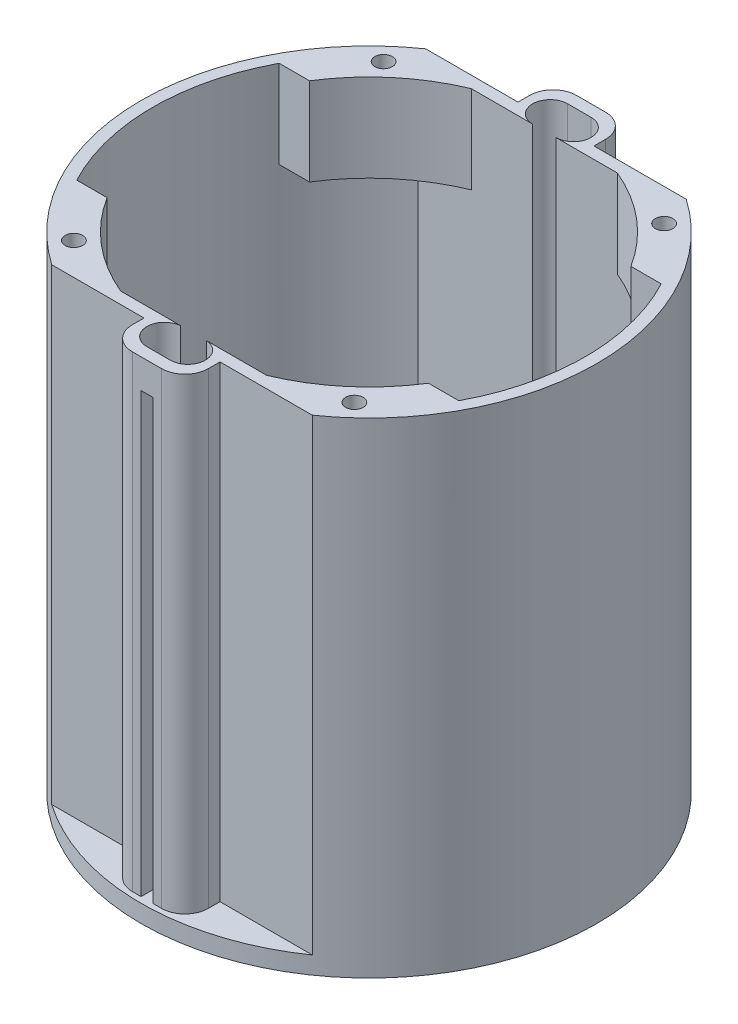
SolidWorks part; units mm, degrees
note: The reader was unsure of these and kept them because the rebuilt part matched: shared geometry of "Croquis1<4>".
material "ABS"
ref_plane "Alzado" through (0, 0, 0) normal (0, 0, 1) x (1, 0, 0)
ref_plane "Planta" through (0, 0, 0) normal (0, 1, 0) x (1, 0, 0)
ref_plane "Vista lateral" through (0, 0, 0) normal (1, 0, 0) x (0, 0, -1)
sketch "Croquis1" plane through (0, 0, 0) normal (0, 1, 0) x (1, 0, 0)
  line L0 (0, 0) -> (73.258, 0) construction
  line L1 (0, 0) -> (0, -19.9451) construction
  line L2 (27.5, 27.6541) -> (27.5, 17.3205)
  line L3 (24.9199, 30) -> (12.5, 30)
  line L4 (-27.5, -27.6541) -> (-27.5, -17.3205)
  line L5 (-27.5, 27.6541) -> (-27.5, 17.3205)
  line L6 (-24.9199, 30) -> (-12.5, 30)
  line L7 (-24.9199, -30) -> (-12.5, -30)
  line L8 (24.9199, -30) -> (12.5, -30)
  line L9 (27.5, -27.6541) -> (27.5, -17.3205)
  arc A0 (-24.9199, 30) -> (-27.5, 27.6541) centre (0, 0) ccw
  circle A1 centre (0, 0) radius 47
  circle A2 centre (0, 0) radius 30
  arc A3 (-12.5, 30) -> (-27.5, 17.3205) centre (0, 0) ccw
  arc A4 (12.5, 30) -> (27.5, 17.3205) centre (0, 0) cw
  arc A6 (24.9199, 30) -> (27.5, 27.6541) centre (0, 0) cw
  arc A7 (-12.5, -30) -> (-27.5, -17.3205) centre (0, 0) cw
  arc A8 (-24.9199, -30) -> (-27.5, -27.6541) centre (0, 0) cw
  arc A9 (-27.5, -27.6541) -> (-24.9199, -30) centre (0, 0) ccw
  arc A10 (24.9199, -30) -> (27.5, -27.6541) centre (0, 0) ccw
  arc A11 (27.5, 27.6541) -> (24.9199, 30) centre (0, 0) ccw
  arc A12 (12.5, -30) -> (27.5, -17.3205) centre (0, 0) ccw
  dimension "D3" = 60
  dimension "D4" = 78
extrude "Saliente-Extruir2" add sketch "Croquis1" along normal blind 80 contours A3 L6 A0 L5 | A8 L7 A7 L4 | A12 L8 A10 L9 | A6 L3 A4 L2
extrude "Saliente-Extruir3" add sketch "Croquis1<4>" against normal blind 3 separate body contours A1 A2 L6 A3 L5 A0 L3 A6 L2 A4 L7 A8 L4 A7 L8 A12 L9 A10 | A2
sketch "Croquis1<4>" plane through (0, 0, 0) normal (0, 1, 0) x (1, 0, 0) same geometry as "Croquis1"
sketch "Croquis2" plane through (0, -3, 0) normal (0, -1, 0) x (1, 0, 0)
  circle A0 centre (0, 0) radius 47
extrude "Saliente-Extruir4" add sketch "Croquis2" against normal up to surface (3 mm away) up to face at (0, 0, 47)
sketch "Croquis3" plane through (0, 80, 0) normal (0, 1, 0) x (1, 0, 0)
  line L0 (-24.9199, 30) -> (-12.5, 30) construction
  line L3 (-27.5, 27.6541) -> (-27.5, 17.3205) construction
  line L4 (0, 0) -> (0, 48.5429) construction
  line L5 (0, 0) -> (-54.4574, 0) construction
  circle A0 centre (-24, 26.5) radius 1.5
  circle A1 centre (24, 26.5) radius 1.5
  circle A2 centre (-24, -26.5) radius 1.5
  circle A3 centre (24, -26.5) radius 1.5
  dimension "D1" = 3.5
  dimension "D3" = 3
  dimension "D2" = 3.5
extrude "Cortar-Extruir1" cut sketch "Croquis3" against normal blind 7
sketch "Croquis4" plane through (0, 0, 0) normal (0, 1, 0) x (1, 0, 0)
  line L0 (-6.5, 30) -> (-4, 30)
  line L1 (-12.5, -30) -> (12.5, -30)
  line L2 (0, 0) -> (57.4423, 0) construction
  line L3 (1, 36) -> (2, 36)
  line L9 (4, 30) -> (6.5, 30)
  line L14 (-1, 38) -> (-2.5, 38)
  line L15 (-6.5, 34) -> (-6.5, 30)
  line L16 (-6.5, 30) -> (-2, 30)
  line L17 (6.5, 30) -> (6.5, 34)
  line L18 (2.5, 38) -> (1, 38)
  line L19 (-2, 36) -> (-1, 36)
  line L20 (-1, 38) -> (-1, 36)
  line L21 (1, 38) -> (1, 36)
  line L22 (0, 37.1225) -> (0, 41.9613) construction
  line L23 (2, 30) -> (6.5, 30)
  line L25 (-12.5, 30) -> (12.5, 30)
  line L34 (2, -30) -> (6.5, -30)
  line L36 (1, -38) -> (1, -36)
  line L37 (-1, -38) -> (-1, -36)
  line L38 (-2, -36) -> (-1, -36)
  line L39 (2.5, -38) -> (1, -38)
  line L40 (6.5, -30) -> (6.5, -34)
  line L41 (-6.5, -30) -> (-2, -30)
  line L42 (-6.5, -34) -> (-6.5, -30)
  line L43 (-1, -38) -> (-2.5, -38)
  line L44 (4, -30) -> (6.5, -30)
  line L45 (1, -36) -> (2, -36)
  line L46 (-6.5, -30) -> (-4, -30)
  line L47 (-6.5, -30) -> (-2, -30)
  circle A0 centre (0, 0) radius 39
  arc A3 (2, 30) -> (2, 36) centre (2, 33) ccw
  arc A4 (-2, 36) -> (-2, 30) centre (-2, 33) ccw
  arc A6 (-2.5, 38) -> (-6.5, 34) centre (-2.5, 34) ccw
  arc A7 (2.232, 30.009) -> (2.5, 30) centre (2.5, 34) ccw
  arc A8 (-2.5, 30) -> (-2.232, 30.009) centre (-2.5, 34) ccw
  arc A9 (6.5, 34) -> (2.5, 38) centre (2.5, 34) ccw
  arc A14 (6.5, -34) -> (2.5, -38) centre (2.5, -34) cw
  arc A15 (-2.5, -30) -> (-2.232, -30.009) centre (-2.5, -34) cw
  arc A16 (2.232, -30.009) -> (2.5, -30) centre (2.5, -34) cw
  arc A17 (-2.5, -38) -> (-6.5, -34) centre (-2.5, -34) cw
  arc A18 (-2, -36) -> (-2, -30) centre (-2, -33) cw
  arc A19 (2, -30) -> (2, -36) centre (2, -33) cw
  dimension "D1" = 4
  dimension "D4" = 4
  dimension "D3" = 4.5
  dimension "D5" = 4
  dimension "D2" = 4.5
extrude "Saliente-Extruir6" add sketch "Croquis4" along normal blind 80 contours A16 A19 L45 L36 L39 A14 L40 L34 | L38 A18 A15 L41 L1 L42 A17 L43 L37 | L23 A3 L3 L21 L18 A9 L17 | L16 A4 L19 L20 L14 A6 L15
sketch "Croquis8" plane through (0, 0, 30) normal (0, 0, 1) x (1, 0, 0)
  line L0 (-24.9199, 80) -> (-6.5, 80)
  line L1 (-6.5, 80) -> (-6.5, 77)
  line L2 (-6.5, 77) -> (-24.9199, 77)
  line L3 (-24.9199, 80) -> (-24.9199, 0) construction
  line L4 (-24.9199, 77) -> (-24.9199, 80)
extrude "Saliente-Extruir7" add sketch "Croquis8" along normal blind 2
sketch "Croquis9" plane through (0, 0, 30) normal (0, 0, 1) x (1, 0, 0)
  line L0 (24.9199, 80) -> (6.5, 80)
  line L1 (6.5, 80) -> (6.5, 77)
  line L2 (6.5, 80) -> (6.5, 0) construction
  line L3 (6.5, 77) -> (24.9199, 77)
  line L4 (24.9199, 80) -> (24.9199, 0) construction
  line L5 (24.9199, 77) -> (24.9199, 80)
extrude "Saliente-Extruir8" add sketch "Croquis9" along normal blind 2
sketch "Croquis10" plane through (0, 0, -30) normal (0, 0, -1) x (-1, 0, 0)
  line L0 (24.9199, 80) -> (6.5, 80)
  line L1 (6.5, 80) -> (6.5, 77)
  line L2 (6.5, 77) -> (24.9199, 77)
  line L3 (24.9199, 80) -> (24.9199, 0) construction
  line L4 (24.9199, 77) -> (24.9199, 80)
extrude "Saliente-Extruir9" add sketch "Croquis10" along normal blind 2
sketch "Croquis11" plane through (0, 0, -30) normal (0, 0, -1) x (-1, 0, 0)
  line L0 (-24.9199, 80) -> (-6.5, 80)
  line L1 (-6.5, 80) -> (-6.5, 77)
  line L2 (-6.5, 80) -> (-6.5, 0) construction
  line L3 (-6.5, 77) -> (-24.9199, 77)
  line L4 (-24.9199, 80) -> (-24.9199, 0) construction
  line L5 (-24.9199, 77) -> (-24.9199, 80)
extrude "Saliente-Extruir10" add sketch "Croquis11" along normal blind 2
sketch "Croquis12" plane through (0, 80, 0) normal (0, 1, 0) x (1, 0, 0)
  circle A0 centre (0, 0) radius 39
  circle A1 centre (0, 0) radius 40.5586
extrude "Cortar-Extruir2" cut sketch "Croquis12" against normal blind 4
sketch "Croquis13" plane through (1, 0, 0) normal (-1, 0, 0) x (0, 0, 1)
  line L0 (36, 80) -> (36, 75)
  line L1 (36, 80) -> (36, 0) construction
  line L2 (36, 75) -> (38, 75)
  line L4 (38, 75) -> (38, 80)
  line L5 (38, 80) -> (38, 0) construction
  line L6 (38, 80) -> (36, 80) construction
  line L7 (38, 80) -> (36, 80)
extrude "Saliente-Extruir11" add sketch "Croquis13" along normal blind 2
sketch "Croquis14" plane through (-1, 0, 0) normal (1, 0, 0) x (0, 0, -1)
  line L0 (38, 80) -> (38, 75)
  line L1 (38, 80) -> (38, 0) construction
  line L2 (38, 75) -> (36, 75)
  line L3 (36, 80) -> (36, 0) construction
  line L4 (36, 75) -> (36, 80)
  line L5 (36, 80) -> (38, 80)
extrude "Saliente-Extruir12" add sketch "Croquis14" along normal blind 2
sketch "Croquis15" plane through (0, 0, 0) normal (0, 1, 0) x (1, 0, 0)
  circle A0 centre (0, 0) radius 39
  circle A1 centre (0, 0) radius 47
extrude "Cortar-Extruir3" cut sketch "Croquis15" against normal blind 3
sketch "Croquis16" plane through (0, 0, 0) normal (0, 1, 0) x (1, 0, 0)
  line L0 (-4.4199, 0) -> (25.967, 0) construction
  line L1 (0, 0) -> (0, 15.8522) construction
  line L2 (-5, 5) -> (-5, 11.4564)
  line L3 (-5, -5) -> (-5, -11.4564)
  line L4 (5, -5) -> (5, -11.4564)
  line L5 (5, 5) -> (5, 11.4564)
  line L6 (-5, 5) -> (-11.4564, 5)
  line L7 (5, 5) -> (11.4564, 5)
  line L8 (5, -5) -> (11.4564, -5)
  line L9 (-5, -5) -> (-11.4564, -5)
  line L10 (5, 16.7705) -> (5, 21.9374)
  line L11 (16.7705, 5) -> (21.9374, 5)
  line L12 (16.7705, -5) -> (21.9374, -5)
  line L13 (5, -16.7705) -> (5, -21.9374)
  line L14 (-5, -16.7705) -> (-5, -21.9374)
  line L15 (-16.7705, -5) -> (-21.9374, -5)
  line L16 (-16.7705, 5) -> (-21.9374, 5)
  line L17 (-5, 16.7705) -> (-5, 21.9374)
  circle A0 centre (-20, 20) radius 1.75
  circle A1 centre (-20, -20) radius 1.75
  circle A2 centre (20, -20) radius 1.75
  circle A3 centre (20, 20) radius 1.75
  arc A5 (-5, 11.4564) -> (-11.4564, 5) centre (0, 0) ccw
  arc A6 (-5, 16.7705) -> (-16.7705, 5) centre (0, 0) ccw
  arc A7 (-5, 21.9374) -> (-21.9374, 5) centre (0, 0) ccw
  arc A9 (5, -11.4564) -> (11.4564, -5) centre (0, 0) ccw
  arc A10 (5, -16.7705) -> (16.7705, -5) centre (0, 0) ccw
  arc A11 (5, -21.9374) -> (21.9374, -5) centre (0, 0) ccw
  arc A12 (21.9374, 5) -> (5, 21.9374) centre (0, 0) ccw
  arc A13 (16.7705, 5) -> (5, 16.7705) centre (0, 0) ccw
  arc A14 (11.4564, 5) -> (5, 11.4564) centre (0, 0) ccw
  arc A15 (-21.9374, -5) -> (-5, -21.9374) centre (0, 0) ccw
  arc A16 (-16.7705, -5) -> (-5, -16.7705) centre (0, 0) ccw
  arc A17 (-11.4564, -5) -> (-5, -11.4564) centre (0, 0) ccw
  dimension "D3" = 3.5
  dimension "D1" = 5
  dimension "D5" = 25
  dimension "D2" = 5
extrude "Cortar-Extruir4" cut sketch "Croquis16" against normal blind 3
sketch "Croquis17" plane through (0, 0, 0) normal (0, 1, 0) x (1, 0, 0)
  line L0 (24.9199, 30) -> (6.5, 30)
  line L1 (6.5, 30) -> (6.5, 32)
  line L2 (6.5, 30) -> (6.5, 34) construction
  line L3 (6.5, 32) -> (22.2935, 32)
  line L4 (0, 0) -> (0, 28.1587) construction
  line L5 (0, 0) -> (34.9804, 0) construction
  line L6 (-6.5, 30) -> (-6.5, 32)
  line L7 (-24.9199, 30) -> (-6.5, 30)
  line L8 (-6.5, 32) -> (-22.2935, 32)
  line L9 (6.5, 32) -> (22.2935, 32)
  line L10 (24.9199, 30) -> (6.5, 30)
  line L11 (6.5, 30) -> (6.5, 32)
  line L12 (-6.5, 32) -> (-22.2935, 32)
  line L13 (-6.5, 30) -> (-6.5, 32)
  line L14 (-24.9199, 30) -> (-6.5, 30)
  line L15 (-24.9199, -30) -> (-6.5, -30)
  line L16 (-6.5, -30) -> (-6.5, -32)
  line L17 (-6.5, -32) -> (-22.2935, -32)
  line L18 (6.5, -30) -> (6.5, -32)
  line L19 (24.9199, -30) -> (6.5, -30)
  line L20 (6.5, -32) -> (22.2935, -32)
  line L21 (-6.5, -32) -> (-22.2935, -32)
  line L22 (-24.9199, -30) -> (-6.5, -30)
  line L23 (-6.5, -30) -> (-6.5, -32)
  line L24 (6.5, -32) -> (22.2935, -32)
  line L25 (6.5, -30) -> (6.5, -32)
  line L26 (24.9199, -30) -> (6.5, -30)
  arc A0 (24.9199, 30) -> (22.2935, 32) centre (0, 0) ccw
  arc A1 (-24.9199, 30) -> (-22.2935, 32) centre (0, 0) cw
  arc A2 (24.9199, 30) -> (22.2935, 32) centre (0, 0) ccw
  arc A3 (-24.9199, 30) -> (-22.2935, 32) centre (0, 0) cw
  arc A4 (24.9199, -30) -> (22.2935, -32) centre (0, 0) cw
  arc A5 (-24.9199, -30) -> (-22.2935, -32) centre (0, 0) ccw
  arc A6 (24.9199, -30) -> (22.2935, -32) centre (0, 0) cw
extrude "Saliente-Extruir13" add sketch "Croquis17" along normal blind 80 contours L0 A0 L3 L1 | A1 L7 L6 L8 | A4 L19 L18 L20 | L15 A5 L17 L16
sketch "Croquis20" plane through (27.5, 0, 0) normal (1, 0, 0) x (0, 0, -1)
  line L1 (-5, 48.6603) -> (-5, 54.1421)
  line L2 (0, 45) -> (0, 40)
  line L4 (5, 74.641) -> (5, 69.5804)
  line L5 (-24.4949, 57.3205) -> (-24.4949, 65)
  line L7 (-5, 5.359) -> (-5, 10.4196)
  line L8 (8.6603, 45) -> (14.1421, 45)
  line L9 (-5, 69.5804) -> (-5, 74.641)
  line L11 (24.4949, 35) -> (19.3649, 35)
  line L14 (-24.4949, 45) -> (-19.3649, 45)
  line L16 (-24.4949, 22.6795) -> (-24.4949, 15)
  line L18 (5, 64.4949) -> (5, 59.3649)
  line L19 (-8.6603, 35) -> (-14.1421, 35)
  line L20 (5, 31.3397) -> (5, 25.8579)
  line L21 (24.4949, 57.3205) -> (24.4949, 65)
  line L22 (24.4949, 22.6795) -> (24.4949, 15)
  line L23 (-5, 15.5051) -> (-5, 20.6351)
  line L24 (5, 10.4196) -> (5, 5.359)
  line L25 (-5, 59.3649) -> (-5, 64.4949)
  line L26 (-14.1421, 45) -> (-8.6603, 45)
  line L27 (5, 54.1421) -> (5, 48.6603)
  line L28 (19.3649, 45) -> (24.4949, 45)
  line L29 (14.1421, 35) -> (8.6603, 35)
  line L30 (5, 20.6351) -> (5, 15.5051)
  line L31 (-5, 25.8579) -> (-5, 31.3397)
  line L32 (-19.3649, 35) -> (-24.4949, 35)
  circle A0 centre (0, 40) radius 5
  arc A1 (-5, 48.6603) -> (-8.6603, 45) centre (0, 40) ccw
  arc A2 (-5, 54.1421) -> (-14.1421, 45) centre (0, 40) ccw
  arc A3 (-5, 59.3649) -> (-19.3649, 45) centre (0, 40) ccw
  arc A4 (-5, 64.4949) -> (-24.4949, 45) centre (0, 40) ccw
  arc A5 (24.4949, 57.3205) -> (5, 69.5804) centre (0, 40) ccw
  arc A6 (24.4949, 65) -> (5, 74.641) centre (0, 40) ccw
  arc A7 (-24.4949, 15) -> (-5, 5.359) centre (0, 40) ccw
  arc A8 (-24.4949, 22.6795) -> (-5, 10.4196) centre (0, 40) ccw
  arc A9 (-5, 74.641) -> (-24.4949, 65) centre (0, 40) ccw
  arc A10 (-5, 69.5804) -> (-24.4949, 57.3205) centre (0, 40) ccw
  arc A11 (-8.6603, 35) -> (-5, 31.3397) centre (0, 40) ccw
  arc A12 (-14.1421, 35) -> (-5, 25.8579) centre (0, 40) ccw
  arc A13 (-19.3649, 35) -> (-5, 20.6351) centre (0, 40) ccw
  arc A14 (-24.4949, 35) -> (-5, 15.5051) centre (0, 40) ccw
  arc A15 (5, 31.3397) -> (8.6603, 35) centre (0, 40) ccw
  arc A16 (5, 25.8579) -> (14.1421, 35) centre (0, 40) ccw
  arc A17 (5, 20.6351) -> (19.3649, 35) centre (0, 40) ccw
  arc A18 (5, 15.5051) -> (24.4949, 35) centre (0, 40) ccw
  arc A19 (5, 10.4196) -> (24.4949, 22.6795) centre (0, 40) ccw
  arc A20 (8.6603, 45) -> (5, 48.6603) centre (0, 40) ccw
  arc A21 (14.1421, 45) -> (5, 54.1421) centre (0, 40) ccw
  arc A22 (19.3649, 45) -> (5, 59.3649) centre (0, 40) ccw
  arc A23 (24.4949, 45) -> (5, 64.4949) centre (0, 40) ccw
  arc A24 (5, 5.359) -> (24.4949, 15) centre (0, 40) ccw
extrude "Cortar-Extruir5" cut sketch "Croquis20" against normal blind 80
sketch "Croquis21" plane through (0, 0, 0) normal (0, 1, 0) x (1, 0, 0)
  line L0 (27.5, 27.6541) -> (27.5, 24.7538)
  line L1 (27.5, 27.6541) -> (27.5, 17.3205) construction
  line L2 (27.5, -27.6541) -> (27.5, -24.7538)
  line L3 (27.5, -27.6541) -> (27.5, -17.3205) construction
  line L4 (-27.5, -27.6541) -> (-27.5, -24.7538)
  line L5 (-27.5, -27.6541) -> (-27.5, -17.3205) construction
  line L6 (-27.5, 27.6541) -> (-27.5, 24.7538)
  line L7 (-27.5, 27.6541) -> (-27.5, 17.3205) construction
  arc A1 (-27.5, 27.6541) -> (-27.5, -27.6541) centre (0, 0) ccw
  arc A3 (-27.5, 24.7538) -> (-27.5, -24.7538) centre (0, 0) ccw
  arc A4 (27.5, -24.7538) -> (27.5, 24.7538) centre (0, 0) ccw
  arc A5 (27.5, -27.6541) -> (27.5, 27.6541) centre (0, 0) ccw
extrude "Saliente-Extruir14" add sketch "Croquis21" along normal blind 80
sketch "Croquis22" plane through (0, 80, 0) normal (0, 1, 0) x (1, 0, 0)
  line L2 (0, 0) -> (0, 32.5) construction
  line L3 (0, 0) -> (33.475, 0) construction
  line L6 (27.5, 24.7538) -> (20.9808, 24.8205)
  line L7 (27.5, 17.3205) -> (32.6956, 17.3205)
  line L8 (27.5, 17.3205) -> (32.6956, 17.3205)
  line L9 (-27.5, -24.7538) -> (-20.9808, -24.8205)
  line L10 (-27.5, -17.3205) -> (-32.6956, -17.3205)
  line L11 (-27.5, -17.3205) -> (-32.6956, -17.3205)
  line L12 (27.5, -17.3205) -> (32.6956, -17.3205)
  line L13 (27.5, -17.3205) -> (32.6956, -17.3205)
  line L14 (27.5, -24.7538) -> (20.9808, -24.8205)
  line L15 (-27.5, 17.3205) -> (-32.6956, 17.3205)
  line L17 (-27.5, 17.3205) -> (-32.6956, 17.3205)
  line L18 (-27.5, 24.7538) -> (-20.9808, 24.8205)
  arc A7 (-27.5, 24.7538) -> (-32.6956, 17.3205) centre (0, 0) ccw
  arc A8 (-27.5, 24.7538) -> (-32.6956, 17.3205) centre (0, 0) ccw
  arc A9 (-12.5, 30) -> (-27.5, 17.3205) centre (0, 0) ccw construction
  arc A11 (-20.9808, 24.8205) -> (-27.5, 17.3205) centre (0, 0) ccw
  arc A12 (20.9808, 24.8205) -> (27.5, 17.3205) centre (0, 0) cw
  arc A13 (27.5, 24.7538) -> (32.6956, 17.3205) centre (0, 0) cw
  arc A14 (27.5, 24.7538) -> (32.6956, 17.3205) centre (0, 0) cw
  arc A15 (-20.9808, -24.8205) -> (-27.5, -17.3205) centre (0, 0) cw
  arc A16 (-27.5, -24.7538) -> (-32.6956, -17.3205) centre (0, 0) cw
  arc A17 (-27.5, -24.7538) -> (-32.6956, -17.3205) centre (0, 0) cw
  arc A18 (27.5, -24.7538) -> (32.6956, -17.3205) centre (0, 0) ccw
  arc A19 (27.5, -24.7538) -> (32.6956, -17.3205) centre (0, 0) ccw
  arc A20 (20.9808, -24.8205) -> (27.5, -17.3205) centre (0, 0) ccw
  arc M3 (-27.5, -24.7538) -> (-27.5, 24.7538) centre (0, 0) cw
  line M4 (-27.5, 24.7538) -> (-27.5, 17.3205)
  arc M5 (-27.5, 17.3205) -> (-12.5, 30) centre (0, 0) cw
  arc M11 (12.5, 30) -> (27.5, 17.3205) centre (0, 0) cw
  line M12 (27.5, 17.3205) -> (27.5, 24.7538)
  arc M13 (27.5, 24.7538) -> (27.5, -24.7538) centre (0, 0) cw
  line M14 (27.5, -24.7538) -> (27.5, -17.3205)
  arc M15 (27.5, -17.3205) -> (12.5, -30) centre (0, 0) cw
  arc M23 (-12.5, -30) -> (-27.5, -17.3205) centre (0, 0) cw
  line M24 (-27.5, -17.3205) -> (-27.5, -24.7538)
extrude "Saliente-Extruir16" add sketch "Croquis22" against normal blind 80 contours L10 M24 M3 | L9 M24 M23 | L12 M14 M13 | L14 M14 M15 | L6 M12 M11 | L7 M12 M13 | L15 M4 M3 | L18 M4 M5
sketch "Croquis25" plane through (0, 0, 0) normal (0, 1, 0) x (1, 0, 0)
  line L0 (27.5, 17.3205) -> (32.6956, 17.3205)
  line L1 (12.5, 30) -> (21.6564, 30)
  line L4 (-12.5, 30) -> (-21.6564, 30)
  line L5 (-27.5, 17.3205) -> (-32.6956, 17.3205)
  line L6 (-27.5, -17.3205) -> (-32.6956, -17.3205)
  line L7 (-12.5, -30) -> (-21.6564, -30)
  line L8 (12.5, -30) -> (21.6564, -30)
  line L9 (27.5, -17.3205) -> (32.6956, -17.3205)
  arc A3 (27.5, 17.3205) -> (12.5, 30) centre (0, 0) ccw
  arc A4 (32.6956, 17.3205) -> (21.6564, 30) centre (0, 0) ccw
  arc A5 (-32.6956, 17.3205) -> (-21.6564, 30) centre (0, 0) cw
  arc A6 (-27.5, 17.3205) -> (-12.5, 30) centre (0, 0) cw
  arc A7 (-27.5, -17.3205) -> (-12.5, -30) centre (0, 0) ccw
  arc A8 (-32.6956, -17.3205) -> (-21.6564, -30) centre (0, 0) ccw
  arc A9 (32.6956, -17.3205) -> (21.6564, -30) centre (0, 0) cw
  arc A10 (27.5, -17.3205) -> (12.5, -30) centre (0, 0) cw
extrude "Cortar-Extruir6" cut sketch "Croquis25" along normal blind 65
sketch "Croquis26" plane through (0, 0, 0) normal (0, 1, 0) x (1, 0, 0)
  line L0 (-23.2692, 14.6558) -> (-27.5, 17.3205)
  line L1 (-23.2692, -14.6558) -> (-27.5, -17.3205)
  line L2 (23.2692, 14.6558) -> (27.5, 17.3205)
  line L3 (23.2692, -14.6558) -> (27.5, -17.3205)
  arc A0 (-23.2692, 14.6558) -> (-23.2692, -14.6558) centre (0, 0) ccw
  arc A2 (-27.5, 17.3205) -> (-27.5, -17.3205) centre (0, 0) ccw
  arc A3 (23.2692, -14.6558) -> (23.2692, 14.6558) centre (0, 0) ccw
  arc A4 (27.5, -17.3205) -> (27.5, 17.3205) centre (0, 0) ccw
extrude "Cortar-Extruir7" cut sketch "Croquis26" against normal blind 65
